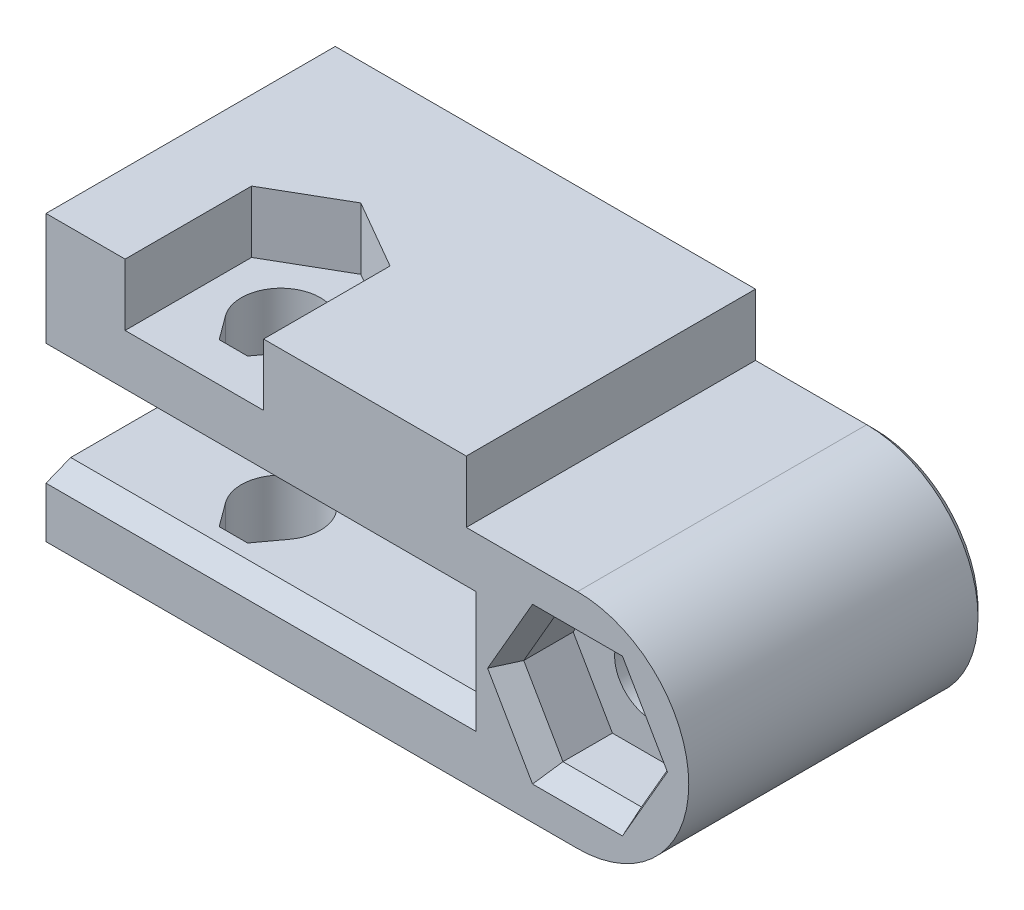
SolidWorks part; units mm, degrees
material "Custom Plastic"
ref_plane "Front Plane" through (0, 0, 0) normal (0, 0, 1) x (1, 0, 0)
ref_plane "Top Plane" through (0, 0, 0) normal (0, 1, 0) x (1, 0, 0)
ref_plane "Right Plane" through (0, 0, 0) normal (1, 0, 0) x (0, 0, -1)
sketch "Sketch1" plane through (0, 0, 0) normal (0, 0, 1) x (1, 0, 0)
  line L0 (-4, 7) -> (-4, -4.5)
  line L1 (22.5, 21.7711) -> (22.5, -13.7573) construction
  line L2 (-4, 0) -> (22.5, 0) construction
  line L3 (13, 4.5) -> (13, 7)
  line L4 (17.5, 4.5) -> (13, 4.5)
  line L5 (13, 7) -> (-4, 7)
  line L7 (-1.5, -1.5) -> (1.5, -1.5) construction
  line L14 (-1.5, 1.5) -> (1.5, 1.5) construction
  line L16 (17.5, -4.5) -> (-4, -4.5)
  circle A0 centre (17.5, 0) radius 1.5
  arc A1 (17.5, -4.5) -> (17.5, 4.5) centre (17.5, 0) ccw
  circle A2 centre (17.5, 0) radius 5 construction
  arc A6 (-1.5, 1.5) -> (-1.5, -1.5) centre (-1.5, 0) ccw construction
  circle A7 centre (0, 0) radius 1.5 construction
  arc A8 (1.5, -1.5) -> (1.5, 1.5) centre (1.5, 0) ccw construction
  dimension "D1" = 26.5
  dimension "D2" = 10
  dimension "D3" = 4.5
  dimension "D4" = 3
  dimension "D5" = 4
  dimension "D6" = 2.5
  dimension "D7" = 17
extrude "Boss-Extrude1" add sketch "Sketch1" along normal blind 12
sketch "Sketch2" plane through (0, 0, 12) normal (0, 0, 1) x (1, 0, 0)
  line L0 (-4, 7) -> (-4, -4.5) construction
  line L1 (13, -2.05) -> (-4, -2.05)
  line L2 (13, 2.05) -> (13, -2.05)
  line L3 (13, 2.05) -> (-4, 2.05)
  line L4 (-4, -2.05) -> (-4, 2.05)
  line L5 (13, -2.05) -> (-4, 2.05) construction
  line L6 (13, 2.05) -> (-4, -2.05) construction
  point P0 (4.5, 0)
  dimension "D1" = 4.1
  dimension "D2" = 17
extrude "Cut-Extrude1" cut sketch "Sketch2" against normal offset from surface (9 mm away) 3 up to face at (9.5833, 2.3333, 0)
sketch "Sketch3" plane through (0, 0, 12) normal (0, 0, 1) x (1, 0, 0)
  line L1 (14.3246, 0) -> (15.9123, -2.75)
  line L2 (15.9123, -2.75) -> (19.0877, -2.75)
  line L3 (19.0877, -2.75) -> (20.6754, 0)
  line L4 (20.6754, 0) -> (19.0877, 2.75)
  line L5 (19.0877, 2.75) -> (15.9123, 2.75)
  line L6 (15.9123, 2.75) -> (14.3246, 0)
  circle A0 centre (17.5, 0) radius 2.75 construction
  dimension "D1" = 5.5
extrude "Cut-Extrude2" cut sketch "Sketch3" against normal blind 3
chamfer "Chamfer1" distance 0.4 distance2 1 9 edges at (4.5, -2.05, 12) (13, 0, 12) (4.5, 2.05, 12) (15.1184, 1.375, 12) (17.5, 2.75, 12) (19.8816, 1.375, 12) (19.8816, -1.375, 12) (15.1184, -1.375, 12) (17.5, -2.75, 12) first distance on face at (17.5, 0, 12)
chamfer "Chamfer2" distance 0.3 angle 45 7 edges at (-4, 1.25, 0) (6.75, -4.5, 0) (22, 0, 0) (15.25, 4.5, 0) (19, 0, 0) (13, 5.75, 0) (4.5, 7, 0)
sketch "Sketch4" plane through (0, -4.5, 0) normal (0, 1, 0) x (1, 0, 0)
  line L0 (-4, -3) -> (13, -3) construction
  line L1 (3.2893, -9.4475) -> (2.5745, -10.42)
  line L2 (2.5745, -10.42) -> (1.4255, -10.42)
  line L3 (1.4255, -10.42) -> (0.7107, -9.4475)
  line L4 (2, -10.42) -> (2, -10.1) construction
  line L5 (-4, -12) -> (-4, -0.3) construction
  arc A0 (3.2893, -9.4475) -> (0.7107, -9.4475) centre (2, -8.5) ccw
  dimension "D1" = 3.2
  dimension "D2" = 5.5
  dimension "D3" = 0.32
  dimension "D4" = 6
extrude "Cut-Extrude3" cut sketch "Sketch4" along normal through all
sketch "Sketch5" plane through (0, 7, 0) normal (0, 1, 0) x (1, 0, 0)
  line L0 (-0.8, -12) -> (4.8, -12)
  line L1 (4.8, -12) -> (4.8, -6.8834)
  line L2 (4.8, -6.8834) -> (2, -5.2668)
  line L3 (2, -5.2668) -> (-0.8, -6.8834)
  line L4 (-0.8, -6.8834) -> (-0.8, -12)
  line L5 (-0.6971, -10.176) -> (2, -11.7332) construction
  line L6 (2, -11.7332) -> (4.8529, -10.086) construction
  line L7 (13, -12) -> (-4, -12) construction
  circle A0 centre (2, -8.5) radius 2.8 construction
  dimension "D1" = 5.6
extrude "Cut-Extrude4" cut sketch "Sketch5" against normal blind 2.5
sketch "Sketch6" plane through (0, 0, 3) normal (0, 0, 1) x (1, 0, 0)
  line L0 (13, -2.05) -> (-4, -2.05) construction
  line L1 (-4, 2.05) -> (-2, 2.05)
  line L2 (-4, 2.05) -> (-4, -2.05)
  line L3 (-4, -2.05) -> (-2, -2.05)
  line L4 (-2, 2.05) -> (-2, -2.05)
  dimension "D1" = 2
extrude "Cut-Extrude5" cut sketch "Sketch6" against normal through all
equation "\"y-plate-thickness\"=4"
equation "\"bed-plate-thickness\"=3"
equation "\"x-plate-thickness\"=5"
equation "\"rod-diameter\"=12"
equation "\"D1@Sketch2\"=\"y-plate-thickness\"+0.1"
